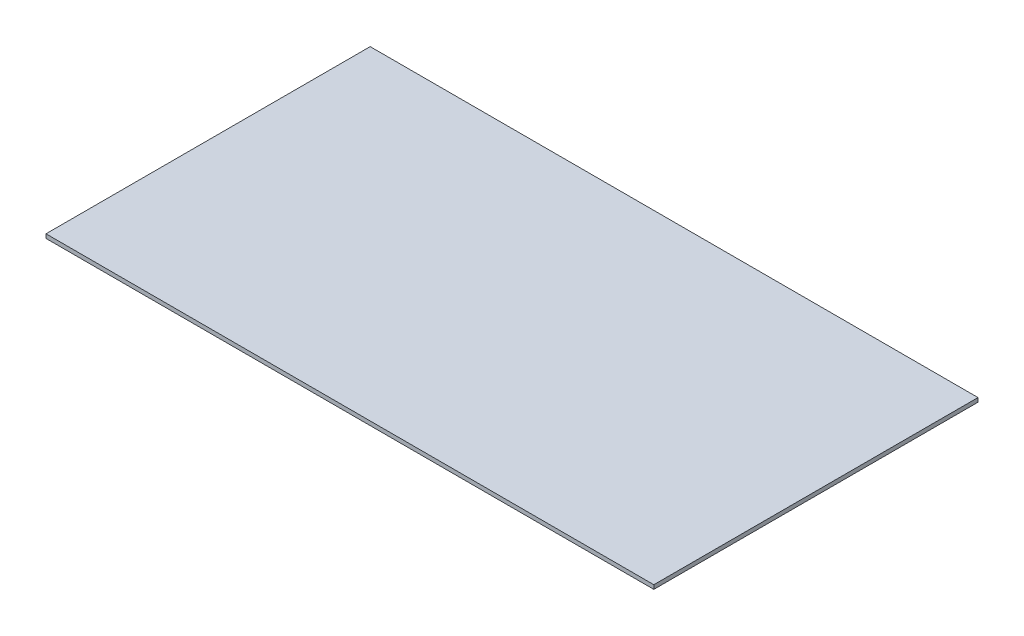
SolidWorks part; units mm, degrees
material "Резина"
ref_plane "Спереди" through (0, 0, 0) normal (0, 0, 1) x (1, 0, 0)
ref_plane "Сверху" through (0, 0, 0) normal (0, 1, 0) x (1, 0, 0)
ref_plane "Справа" through (0, 0, 0) normal (1, 0, 0) x (0, 0, -1)
sketch "Эскиз1" plane through (0, 0, 0) normal (0, 1, 0) x (1, 0, 0)
  line L1 (-750, -400) -> (750, -400)
  line L2 (-750, -400) -> (-750, 400)
  line L3 (-750, 400) -> (750, 400)
  line L4 (750, -400) -> (750, 400)
  line L5 (0, 400) -> (0, -400) construction
  line L6 (-750, 0) -> (750, 0) construction
  point P0 (0, 0)
  dimension "D1" = 800
  dimension "D2" = 1500
extrude "Бобышка-Вытянуть1" add sketch "Эскиз1" along normal blind 10
equation "\"длина стола\"= 1500"
equation "\"D2@Эскиз1\"=\"длина стола\""
